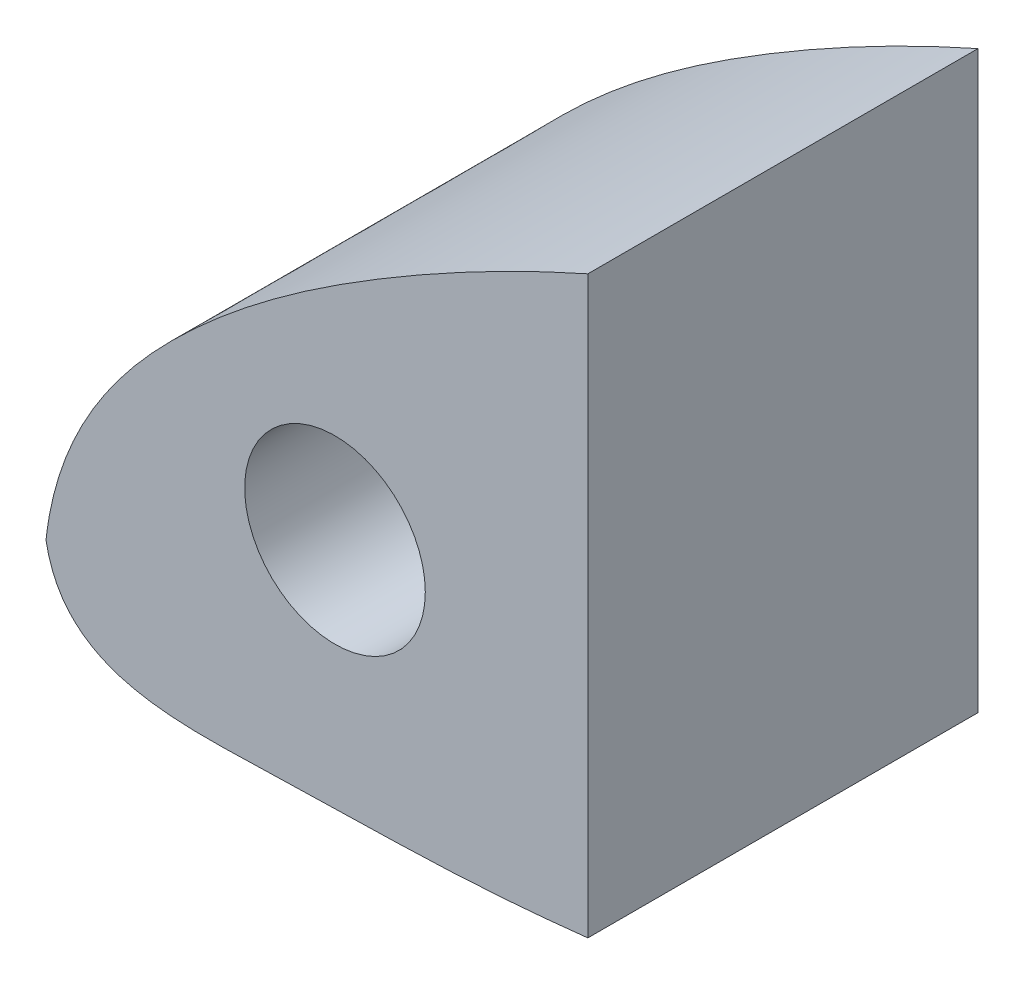
SolidWorks part; units mm, degrees
ref_plane "Front Plane" through (0, 0, 0) normal (0, 0, 1) x (1, 0, 0)
ref_plane "Top Plane" through (0, 0, 0) normal (0, 1, 0) x (1, 0, 0)
ref_plane "Right Plane" through (0, 0, 0) normal (1, 0, 0) x (0, 0, -1)
sketch "Sketch1" plane through (0, 0, 0) normal (0, 0, 1) x (1, 0, 0)
  spline S0 degree 3 poles (0.0006, 0.0001) (0.8106, 7.3592) (8.6491, 17.8566) (26.2867, 29.9752) (52.1111, 42.0692) (89.5976, 49.2908) (131.4008, 47.8848) (173.2567, 40.0411) (217.9611, 29.613) (256.9521, 19.5289) (290.3598, 8.711) (301.2732, 4.3828) (314.8169, -0.5162) (309.8463, 0.0001) knots 0 0 0 0 0.060864 0.113688 0.188609 0.312909 0.448482 0.557612 0.691544 0.852438 0.929756 0.976058 1 1 1 1
  spline S1 degree 3 poles (309.8463, 0.0001) (303.9568, 1.471) (293.9895, 2.094) (276.264, 4.5144) (260.8463, 5.4274) (235.8588, 7.8703) (205.1014, 8.8381) (157.7186, 9.0307) (110.4973, 6.1815) (66.5062, -0.5867) (36.4547, -6.0985) (15.3166, -6.1891) (1.2307, -6.9241) (0.0006, 0.0001) knots 0 0 0 0 0.057787 0.095275 0.171021 0.205339 0.335319 0.464904 0.658702 0.785512 0.893517 0.943092 1 1 1 1
extrude "Boss-Extrude1" add sketch "Sketch1" along normal blind 27.432
sketch "Sketch2" plane through (0, 0, 27.432) normal (0, 0, 1) x (1, 0, 0)
  circle A0 centre (20.32, 10.16) radius 6.35
  circle A1 centre (227.2963, 19.0501) radius 3.175
  dimension "D2" = 12.7
  dimension "D3" = 6.35
  dimension "D6" = 20.32
  dimension "D1" = 82.55
  dimension "D4" = 19.05
  dimension "D5" = 10.16
extrude "Cut-Extrude1" cut sketch "Sketch2" against normal through all
sketch "Sketch3" plane through (0, 0, 27.432) normal (0, 0, 1) x (1, 0, 0)
  line L1 (38.1, 71.718) -> (331.2889, 71.718)
  line L2 (38.1, 71.718) -> (38.1, -66.2532)
  line L3 (38.1, -66.2532) -> (331.2889, -66.2532)
  line L4 (331.2889, 71.718) -> (331.2889, -66.2532)
  dimension "D1" = 38.1
extrude "Cut-Extrude2" cut sketch "Sketch3" against normal through all
